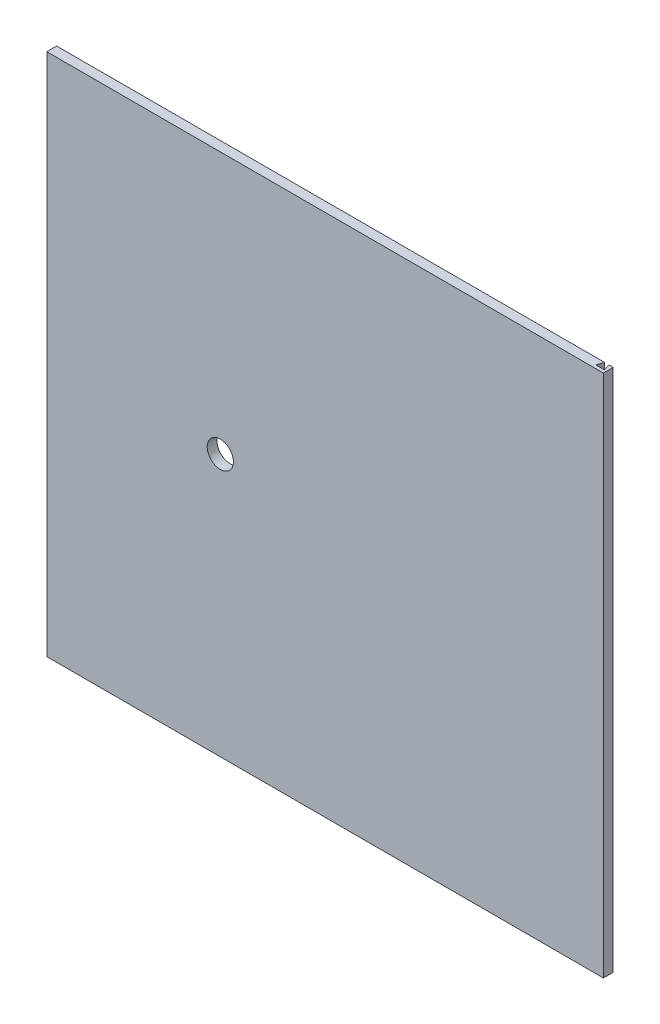
SolidWorks part; units mm, degrees
ref_plane "Front Plane" through (0, 0, 0) normal (0, 0, 1) x (1, 0, 0)
ref_plane "Top Plane" through (0, 0, 0) normal (0, 1, 0) x (1, 0, 0)
ref_plane "Right Plane" through (0, 0, 0) normal (1, 0, 0) x (0, 0, -1)
sketch "Sketch1" plane through (0, 0, 0) normal (0, 0, 1) x (1, 0, 0)
  line L1 (0, 0) -> (85, 0)
  line L2 (0, 0) -> (0, 80)
  line L3 (0, 80) -> (85, 80)
  line L4 (85, 0) -> (85, 80)
  dimension "D1" = 80
  dimension "D2" = 85
extrude "Boss-Extrude1" add sketch "Sketch1" along normal blind 1.5
sketch "Sketch2" plane through (0, 80, 0) normal (0, 1, 0) x (1, 0, 0)
  line L1 (84.65, -1) -> (85, -1) construction
  line L8 (85, -1.5) -> (85, 0) construction
  line L9 (84.65, -1) -> (84.325, 0)
  line L10 (83.35, -1) -> (84.65, -1)
  line L11 (83.35, -1) -> (83.675, 0)
  line L12 (84.325, 0) -> (83.675, 0)
  dimension "D1" = 0.35
extrude "Cut-Extrude1" cut sketch "Sketch2" against normal up to surface (80 mm away) up to face at (42.5, 0, 0.75)
sketch "Sketch3" plane through (0, 0, 1.5) normal (0, 0, 1) x (1, 0, 0)
  circle A2 centre (26.5, 40) radius 2
extrude "Cut-Extrude4" cut sketch "Sketch3" against normal up to surface (1.5 mm away) contours A2 up to face at (41.8375, 40, 0)
